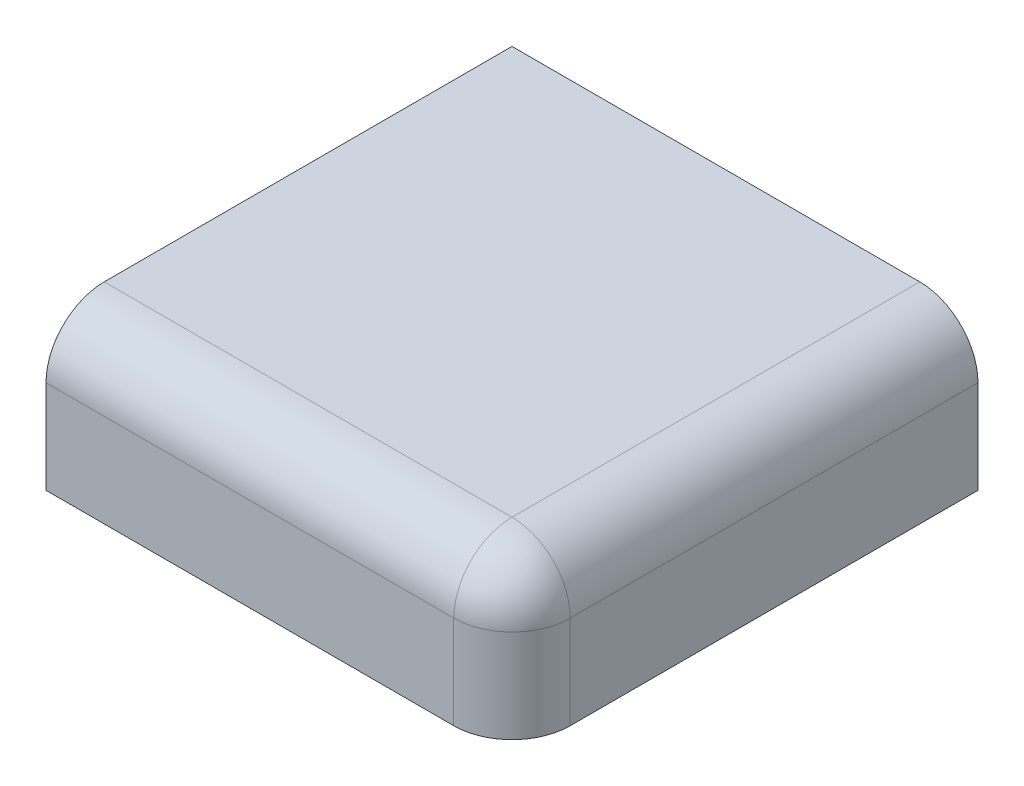
SolidWorks part; units mm, degrees
ref_plane "Front Plane" through (0, 0, 0) normal (0, 0, 1) x (1, 0, 0)
ref_plane "Top Plane" through (0, 0, 0) normal (0, 1, 0) x (1, 0, 0)
ref_plane "Right Plane" through (0, 0, 0) normal (1, 0, 0) x (0, 0, -1)
sketch "Эскиз1" plane through (0, 0, 0) normal (0, 1, 0) x (1, 0, 0)
  line L0 (-20, -20) -> (20, -20)
  line L1 (-20, -20) -> (-20, 20)
  line L2 (20, -20) -> (20, 20)
  line L3 (-20, 20) -> (20, 20)
  line L4 (-20, -20) -> (20, 20) construction
  line L5 (20, -20) -> (-20, 20) construction
  point P1 (0, 0)
  dimension "D1" = 40
  dimension "D2" = 40
extrude "Бобышка-Вытянуть1" add sketch "Эскиз1" against normal blind 13
sketch "Эскиз7" plane through (-20, 0, 0) normal (-1, 0, 0) x (0, 0, 1)
  line L0 (0, 8.7545) -> (0, -21.4501) construction
  line L1 (-28.759, -6.5) -> (30.1285, -6.5) construction
  line L2 (-20, 0) -> (20, 0) construction
  line L3 (-20, -13) -> (20, -13) construction
  line L4 (-10, 5.2438) -> (-10, -20.548) construction
  line L5 (-10, -2.1098) -> (-12.0375, -3.2861)
  line L6 (-10, -2.1098) -> (-7.9625, -3.2861)
  line L8 (-20, -13) -> (-20, 0) construction
  line L9 (10, -2.1098) -> (12.0375, -3.2861)
  line L10 (10, -2.1098) -> (7.9625, -3.2861)
  circle A0 centre (-10, -6.8152) radius 4.075
  circle A1 centre (10, -6.8152) radius 4.075
  point P15 (-10, -10.8902)
  point P21 (10, -10.8902)
  dimension "D2" = 8.15
  dimension "D3" = 11.85
  dimension "D1" = 60
extrude "Вырез-Вытянуть2" cut sketch "Эскиз7" against normal blind 2.15 contours A0 | A0 L6 L5 | A1 | L10 A1 L9 region at (-20, -2.6034, -10) region at (-20, -6.8152, -10) region at (-20, -2.6034, 10) region at (-20, -6.8152, 10)
pattern_circular "Круговой массив1" count 2 over 90 about axis through (0, -13, 0) along (0, -1, 0) of "Вырез-Вытянуть2"
fillet "Скругление2" radius 5 3 edges at (0, 0, 20) (20, 0, 0) (20, -6.5, 20)
